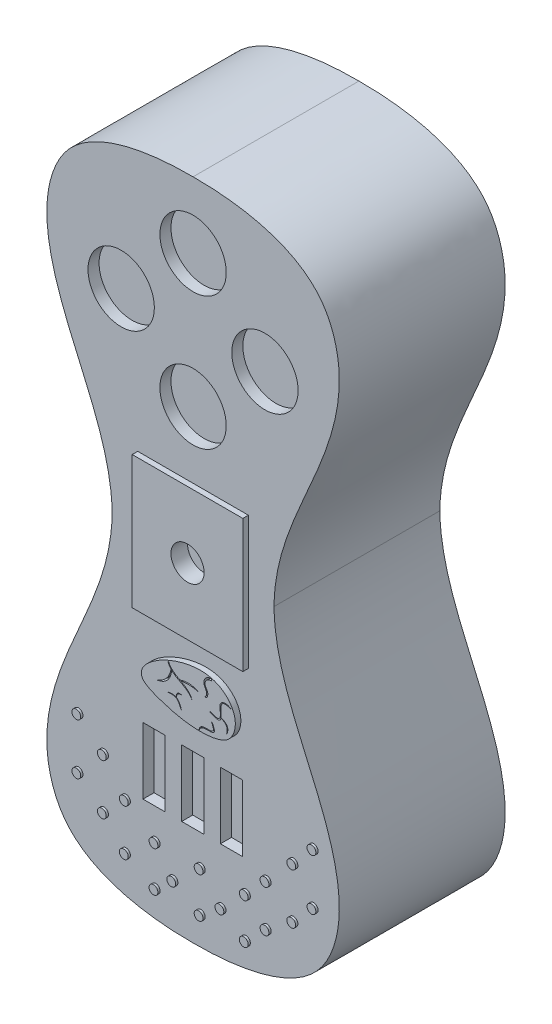
SolidWorks part; units mm, degrees
ref_plane "Alzado" through (0, 0, 0) normal (0, 0, 1) x (1, 0, 0)
ref_plane "Planta" through (0, 0, 0) normal (0, 1, 0) x (1, 0, 0)
ref_plane "Vista lateral" through (0, 0, 0) normal (1, 0, 0) x (0, 0, -1)
sketch "Croquis1" plane through (0, 0, 0) normal (0, 0, 1) x (1, 0, 0)
  line L1 (-5, 6) -> (5, 6)
  line L2 (5, 6) -> (5, -6)
  line L3 (-5, 6) -> (-5, -6)
  line L4 (-5, -6) -> (5, -6)
  line L5 (2.4714, -14.9997) -> (2.4714, -20.9997)
  line L6 (-1.0286, -14.9997) -> (0.9714, -14.9997)
  line L7 (0.9714, -14.9997) -> (0.9714, -20.9997)
  line L8 (0.9714, -20.9997) -> (-1.0286, -20.9997)
  line L9 (-1.0286, -20.9997) -> (-1.0286, -14.9997)
  line L10 (2.4714, -20.9997) -> (4.4714, -20.9997)
  line L11 (4.4714, -20.9997) -> (4.4714, -14.9997)
  line L12 (4.4714, -14.9997) -> (2.4714, -14.9997)
  line L13 (-2.5286, -14.9997) -> (-2.5286, -20.9997)
  line L14 (-2.5286, -20.9997) -> (-4.5286, -20.9997)
  line L15 (-4.5286, -20.9997) -> (-4.5286, -14.9997)
  line L16 (-4.5286, -14.9997) -> (-2.5286, -14.9997)
  circle A0 centre (0, 0) radius 1.5
  circle A5 centre (6.5, 18) radius 3
  circle A6 centre (0, 12) radius 3
  circle A7 centre (-6.5, 18) radius 3
  circle A8 centre (0, 24) radius 3
  spline S0 degree 3 poles (0, 30) (3.518, 30.0252) (10.8325, 29.2451) (13.7343, 21.4363) (11.9497, 12.1508) (7.407, 5.6845) (7.3158, 0) knots 0 0 0 0 0.312025 0.415095 0.592639 1 1 1 1
  spline S1 degree 3 poles (0, 30) (-3.518, 30.0252) (-10.8325, 29.2451) (-13.7343, 21.4363) (-11.9497, 12.1508) (-7.407, 5.6845) (-7.3158, 0) knots 0 0 0 0 0.312025 0.415095 0.592639 1 1 1 1
  spline S2 degree 3 poles (0, -30) (3.518, -30.0252) (10.8325, -29.2451) (13.7343, -21.4363) (11.9497, -12.1508) (7.407, -5.6845) (7.3158, 0) knots 0 0 0 0 0.312025 0.415095 0.592639 1 1 1 1
  spline S3 degree 3 poles (0, -30) (-3.518, -30.0252) (-10.8325, -29.2451) (-13.7343, -21.4363) (-11.9497, -12.1508) (-7.407, -5.6845) (-7.3158, 0) knots 0 0 0 0 0.312025 0.415095 0.592639 1 1 1 1
  point P4 (0, 0)
  point P9 (0, 0)
extrude "Saliente-Extruir1" add sketch "Croquis1" along normal blind 15 contours S3 S2 S0 S1 A7 A6 A5 L4 L3 L1 L2 A8 region at (12.4715, 19.1377, 0)
extrude "Saliente-Extruir4" add sketch "Croquis1<5>" along normal blind 14 contours A8 | A5 | A6 | L9 L8 L7 L6 | L11 L12 L5 L10 | A7 | A0 | L15 L16 L13 L14 region at (3.4714, -17.9997, 0) region at (-0.0286, -17.9997, 0) region at (6.5, 18, 0) region at (0, 12, 0) region at (0, 24, 0)
sketch "Croquis1<5>" plane through (0, 0, 0) normal (0, 0, 1) x (1, 0, 0) same geometry as "Croquis1"
extrude "Saliente-Extruir5" add sketch "Croquis1<6>" along normal blind 15.5 contours L3 L4 L2 L1 A0 region at (0, 5.8438, 0)
sketch "Croquis1<6>" plane through (0, 0, 0) normal (0, 0, 1) x (1, 0, 0) same geometry as "Croquis1"
sketch "Croquis2" plane through (0, 0, 0) normal (0, 1, 0) x (1, 0, 0)
  line L1 (0, -15) -> (0, 0) construction
  line L3 (0, -8.5) -> (1.2, -8.5)
  line L4 (1.2, -8.5) -> (1.2, -7.5)
  line L5 (1.2, -7.5) -> (0, -7.5)
  line L6 (0, -7.5) -> (-1.2, -7.5)
  line L7 (0, -8.5) -> (-1.2, -8.5)
  line L8 (-1.2, -8.5) -> (-1.2, -7.5)
extrude "Cortar-Extruir2" cut sketch "Croquis2" against normal blind 10.5 from offset 29.5 offset against normal yes
ref_plane "Plano1" through (0, 0, 15) normal (0, 0, 1) x (1, 0, 0)
sketch "Croquis3" plane through (0, 0, 15) normal (0, 0, 1) x (1, 0, 0)
  line L0 (0.933, -9.5631) -> (0.933, -9.5868)
  line L1 (-1.4923, -9.0656) -> (-1.4426, -9.119)
  line L2 (-1.0342, -11.0102) -> (-1.0086, -11.0257)
  line L3 (-1.7688, -10.9868) -> (-1.7419, -11.0032)
  line L4 (-0.5548, -11.803) -> (-0.5806, -11.7881)
  line L5 (2.1841, -11.3662) -> (2.2392, -11.3902)
  line L7 (1.9401, -10.5986) -> (1.995, -10.5986)
  line L8 (3.0439, -10.5986) -> (3.0384, -10.6415)
  line L9 (3.5429, -11.5802) -> (3.5429, -11.6377)
  line L10 (1.0556, -12.475) -> (1.0556, -12.5556)
  line L11 (2.1841, -8.0274) -> (2.1841, -8.1732)
  circle A0 centre (-8.0511, -23.7746) radius 0.4
  circle A1 centre (-6.0643, -25.976) radius 0.4
  circle A2 centre (-3.3796, -23.7746) radius 0.4
  circle A3 centre (-1.7688, -25.976) radius 0.4
  circle A4 centre (0.7012, -23.7746) radius 0.4
  circle A5 centre (2.5805, -25.976) radius 0.4
  circle A6 centre (4.782, -23.7746) radius 0.4
  circle A7 centre (6.6613, -25.576) radius 0.4
  circle A8 centre (9.0776, -23.7746) radius 0.4
  circle A9 centre (4.782, -27.4258) radius 0.4
  circle A10 centre (0.7012, -27.4258) radius 0.4
  circle A11 centre (-3.3796, -27.4258) radius 0.4
  circle A12 centre (-10.3599, -21.7878) radius 0.4
  circle A13 centre (-8.0511, -19.2105) radius 0.4
  circle A14 centre (-10.3599, -17.1701) radius 0.4
  circle A15 centre (-6.0643, -21.7878) radius 0.4
  circle A16 centre (6.6613, -21.7878) radius 0.4
  circle A17 centre (10.9032, -21.7878) radius 0.4
  circle A18 centre (9.0776, -19.2105) radius 0.4
  circle A19 centre (10.9032, -17.1701) radius 0.4
  spline S0 degree 3 poles (-6.3095, -10.4729) (-1.749, -12.2497) (0.4604, -12.724) (2.5865, -12.5521) (3.9007, -11.9498) (4.8369, -9.9826) (1.7124, -5.9508) (-6.3095, -10.4729) (-1.749, -12.2497) (0.4604, -12.724) knots -0.607578 -0.436397 -0.086451 0 0.177359 0.280438 0.308801 0.392422 0.563603 0.913549 1 1.177359 1.280438 1.308801 only from (-2.4644, -11.9411) to (-2.4644, -11.9411)
  spline S1 degree 3 poles (-1.7688, -8.5743) (-1.4433, -9.6394) (0.0026, -9.5762) (0.435, -10.5986) knots 0 0 0 0 1 1 1 1
  spline S2 degree 2 poles (-0.6809, -9.5032) (0.1112, -9.1995) (0.933, -9.5631) knots 0 0 0 1 1 1
  spline S3 degree 2 poles (-1.4426, -9.119) (-1.5531, -10.3451) (-2.7786, -10.5395) knots 0 0 0 1 1 1
  spline S4 degree 3 poles (4.0869, -9.5532) (1.8332, -8.5474) (4.2583, -11.8503) (1.9401, -10.5986) knots 0 0 0 0 1 1 1 1
  spline S5 degree 2 poles (3.0439, -10.5986) (3.8876, -10.8757) (3.5429, -11.6377) knots 0 0 0 1 1 1
  spline S6 degree 3 poles (1.0556, -12.475) (1.2574, -11.6083) (2.8145, -12.7181) (2.1841, -11.3662) knots 0 0 0 0 1 1 1 1
  spline S7 degree 2 poles (-0.5548, -11.803) (-0.7936, -10.7074) (-1.7688, -10.9868) knots 0 0 0 1 1 1
  spline S8 degree 2 poles (-1.0342, -11.0102) (-0.993, -10.4785) (-0.5534, -10.5986) knots 0 0 0 1 1 1
  spline S9 degree 1 poles (-1.7688, -8.5743) (-1.7109, -8.5705) knots 0 0 1 1
  spline S10 degree 3 poles (-1.7109, -8.5705) (-1.3189, -9.5618) (0.1041, -9.4916) (0.435, -10.5986) knots 0 0 0 0 1 1 1 1
  spline S11 degree 1 poles (-0.6809, -9.5032) (-0.6151, -9.5381) knots 0 0 1 1
  spline S12 degree 2 poles (-0.6151, -9.5381) (0.1611, -9.3698) (0.933, -9.5868) knots 0 0 0 1 1 1
  spline S13 degree 2 poles (-2.7786, -10.5395) (-1.6926, -10.1374) (-1.4923, -9.0656) knots 0 0 0 1 1 1
  spline S14 degree 3 poles (-1.7419, -11.0032) (-1.5033, -10.9552) (-1.0897, -10.9554) (-0.7434, -11.3544) (-0.6604, -11.5885) (-0.5806, -11.7881) knots 0 0 0 0 0.545869 0.587414 1 1 1 1
  spline S15 degree 2 poles (-1.0086, -11.0257) (-0.9782, -10.5957) (-0.5534, -10.5986) knots 0 0 0 1 1 1
  spline S16 degree 3 poles (2.2392, -11.3902) (2.9852, -12.7845) (1.2874, -11.6719) (1.0556, -12.5556) knots 0 0 0 0 1 1 1 1
  spline S17 degree 3 poles (1.995, -10.5986) (2.1342, -10.6214) (2.9516, -11.0583) (2.9996, -10.1043) (2.8384, -9.4579) (3.545, -9.1754) (3.8836, -9.4414) (4.0869, -9.5532) knots 0 0 0 0 0.257519 0.429653 0.660166 0.781442 1 1 1 1
  spline S18 degree 2 poles (3.0384, -10.6415) (3.7259, -10.8738) (3.5429, -11.5802) knots 0 0 0 1 1 1
  spline S19 degree 3 poles (2.1841, -8.0274) (1.7964, -7.8966) (1.0609, -8.7427) (1.9677, -9.2835) (1.5738, -9.6851) knots 0 0 0 0 0.501897 1 1 1 1
  spline S20 degree 3 poles (2.1841, -8.1732) (1.8939, -8.0626) (1.3072, -8.6632) (1.9638, -9.1582) (1.7708, -9.7363) (1.5738, -9.6851) knots 0 0 0 0 0.420925 0.741921 1 1 1 1
  point P104 (1.0556, -12.5556)
  point P108 (1.0556, -12.475)
  point P110 (4.0869, -9.5532)
  point P112 (-0.6809, -9.5032)
  point P113 (-1.4923, -9.0656)
  point P114 (-1.4426, -9.119)
  point P115 (-1.0342, -11.0102)
  point P116 (-1.0086, -11.0257)
  point P117 (3.0439, -10.5986)
  point P118 (3.0384, -10.6415)
extrude "Saliente-Extruir6" add sketch "Croquis3" along normal blind 0.2 contours A1 | A3 | A8 | A7 | A5 | A14 | A13 | A12 | A15 | A0 | A2 | A11 | A4 | A6 | A16 | A18 | A19 | A17 | A9 | A10 region at (-6.0643, -25.976, 15) region at (-1.7688, -25.976, 15) region at (2.5805, -25.976, 15) region at (6.6613, -25.576, 15) region at (9.0776, -23.7746, 15)
extrude "Saliente-Extruir7" add sketch "Croquis3<3>" along normal blind 0.5 contours S0 region at (0.3561, -10.3147, 15)
sketch "Croquis3<3>" plane through (0, 0, 15) normal (0, 0, 1) x (1, 0, 0) same geometry as "Croquis3"
